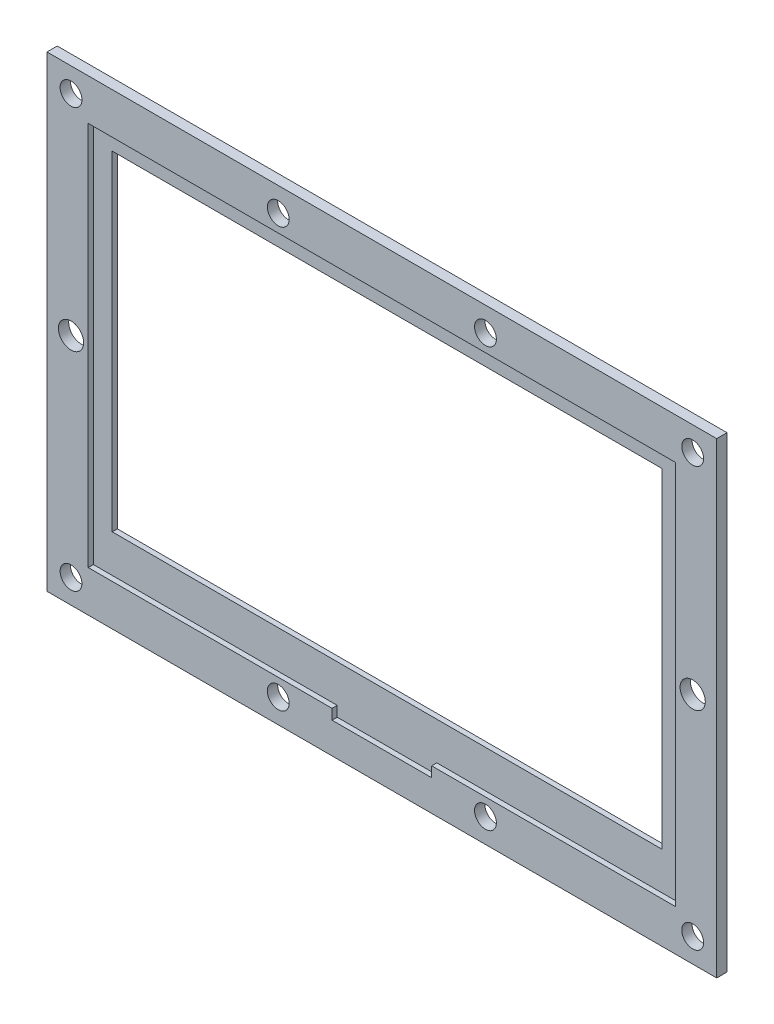
SolidWorks part; units mm, degrees
ref_plane "Front Plane" through (0, 0, 0) normal (0, 0, 1) x (1, 0, 0)
ref_plane "Top Plane" through (0, 0, 0) normal (0, 1, 0) x (1, 0, 0)
ref_plane "Right Plane" through (0, 0, 0) normal (1, 0, 0) x (0, 0, -1)
sketch "Sketch1" plane through (0, 0, 0) normal (0, 0, 1) x (1, 0, 0)
  line L1 (85.5, -56) -> (-85.5, -56)
  line L2 (85.5, -56) -> (85.5, 56)
  line L3 (85.5, 56) -> (-85.5, 56)
  line L4 (-85.5, -56) -> (-85.5, 56)
  line L5 (85.5, -56) -> (-85.5, 56) construction
  line L6 (85.5, 56) -> (-85.5, -56) construction
  line L11 (80, -45) -> (-80, -45)
  line L12 (80, -45) -> (80, 51)
  line L13 (80, 51) -> (-80, 51)
  line L14 (-80, -45) -> (-80, 51)
  line L15 (80, -45) -> (-80, 51) construction
  line L16 (80, 51) -> (-80, -45) construction
  line L17 (-14.5, -56) -> (14.5, -56)
  line L18 (-14.5, -56) -> (-14.5, -59)
  line L19 (-14.5, -59) -> (14.5, -59)
  line L20 (14.5, -56) -> (14.5, -59)
  line L21 (97.5, 68) -> (-97.5, 68)
  line L22 (97.5, 68) -> (97.5, -68)
  line L23 (97.5, -68) -> (-97.5, -68)
  line L24 (-97.5, 68) -> (-97.5, -68)
  line L25 (97.5, 68) -> (-97.5, -68) construction
  line L26 (97.5, -68) -> (-97.5, 68) construction
  point P0 (0, 0)
  point P6 (0, 0)
  point P7 (0, 3)
  point P16 (0, 0)
  dimension "D1" = 171
  dimension "D2" = 112
  dimension "D3" = 96
  dimension "D4" = 160
  dimension "D5" = 5
  dimension "D6" = 71
  dimension "D7" = 29
  dimension "D8" = 3
  dimension "D9" = 12
  dimension "D10" = 17.5
  dimension "D11" = 12
extrude "Boss-Extrude1" add sketch "Sketch1" against normal blind 1.5 contours L4 L1 L2 L3 L11 L14 L13 L12 | L21 L24 L23 L22 L1 L20 L19 L18 L4 L3 L2 | L20 L1 L18 L19 region at (50, -53.9559, 0) region at (0, -57.5, 0) region at (95.1226, 0, 0)
extrude "Boss-Extrude2" add sketch "Sketch1<3>" along normal blind 1.5 contours L21 L24 L23 L22 L1 L20 L19 L18 L4 L3 L2 region at (95.1226, 0, 0)
sketch "Sketch1<3>" plane through (0, 0, 0) normal (0, 0, 1) x (1, 0, 0) same geometry as "Sketch1"
sketch "Sketch2" plane through (0, 0, 1.5) normal (0, 0, 1) x (1, 0, 0)
  line L0 (97.5, 68) -> (-97.5, 68) construction
  line L1 (90.5, -61) -> (-90.5, -61) construction
  line L2 (90.5, -61) -> (90.5, 61) construction
  line L3 (90.5, 61) -> (-90.5, 61) construction
  line L4 (-90.5, -61) -> (-90.5, 61) construction
  line L5 (90.5, -61) -> (-90.5, 61) construction
  line L6 (90.5, 61) -> (-90.5, -61) construction
  line L7 (-97.5, 68) -> (-97.5, -68) construction
  line L8 (-90.5, 61) -> (-30.1667, 61) construction
  line L9 (-30.1667, 61) -> (30.1667, 61) construction
  line L10 (30.1667, 61) -> (90.5, 61) construction
  line L11 (-90.5, 61) -> (-30.1667, 61) construction
  line L12 (-30.1667, 61) -> (30.1667, 61) construction
  line L13 (30.1667, 61) -> (90.5, 61) construction
  line L14 (90.5, 61) -> (90.5, 0) construction
  line L15 (90.5, 0) -> (90.5, -61) construction
  circle A0 centre (-90.5, 61) radius 3.175
  circle A2 centre (90.5, 61) radius 3.175
  circle A3 centre (90.5, -61) radius 3.175
  circle A5 centre (-90.5, -61) radius 3.175
  circle A6 centre (-30.1667, -61) radius 3.175
  circle A7 centre (30.1667, -61) radius 3.175
  circle A8 centre (90.5, 0) radius 3.6737
  circle A9 centre (-30.1667, 61) radius 3.175
  circle A10 centre (30.1667, 61) radius 3.175
  circle A11 centre (-90.5, 0) radius 3.6737
  point P0 (0, 0)
  dimension "D1" = 6.35
  dimension "D2" = 7
  dimension "D3" = 7
extrude "Cut-Extrude1" cut sketch "Sketch2" against normal through all
